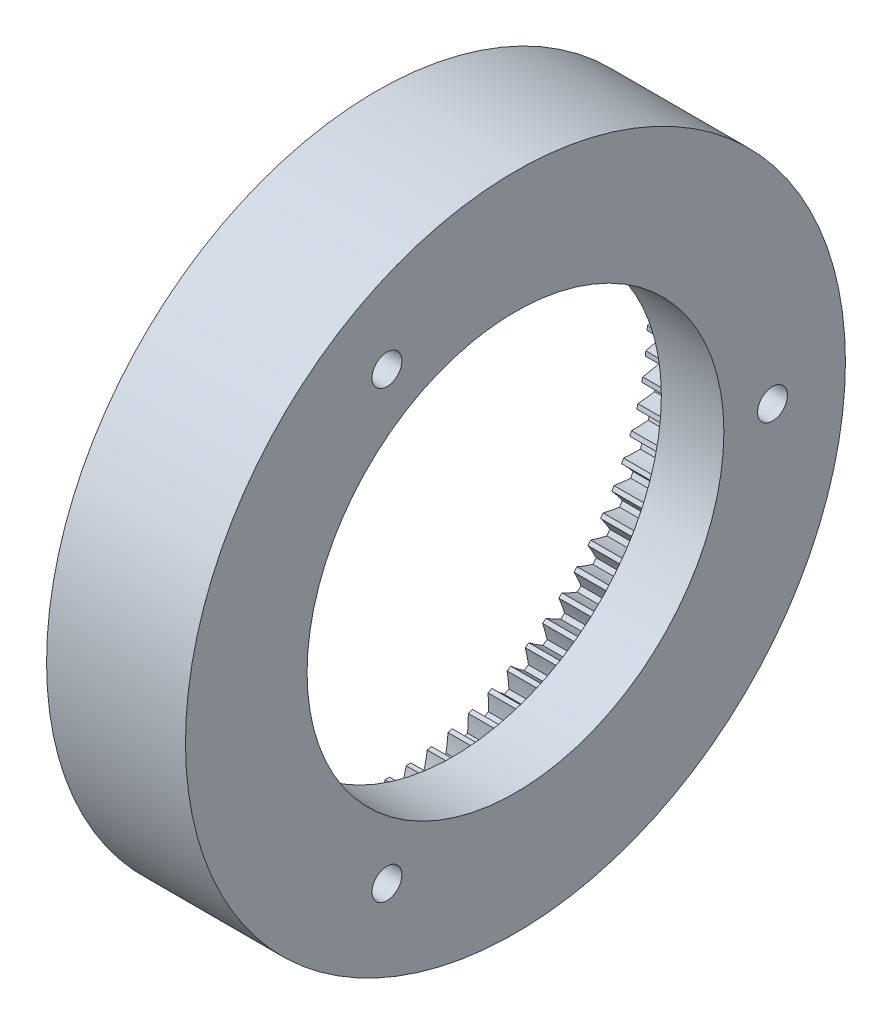
SolidWorks part; units mm, degrees
ref_plane "Plane1" through (0, 0, 0) normal (0, 0, 1) x (1, 0, 0)
ref_plane "Plane2" through (0, 0, 0) normal (0, 1, 0) x (1, 0, 0)
ref_plane "Plane3" through (0, 0, 0) normal (1, 0, 0) x (0, 0, -1)
other "Configuration Table"
sketch "HoldingSke" plane through (0, 0, 0) normal (0, 1, 0) x (1, 0, 0)
  line L0 (0, 0) -> (0.1736, -0.9848)
  line L1 (-15, 0) -> (100, 0) construction
  line L2 (0, 0) -> (-2.1039, 2.3779)
  line L3 (0, 0) -> (-11.863, 4.5341)
  line L4 (0, 0) -> (1.4996, 8.5048)
  line L5 (0, 0) -> (-23.7986, -8.8762)
  line L6 (0, 0) -> (-10.5278, -7.1032)
  line L7 (-2.1039, 2.3779) -> (3.3635, 27.1825)
  line L8 (-76.2, 3.3779) -> (-54.61, 3.3779)
  line L9 (-71.009, 38.7566) -> (-53.1078, 45.2721)
  line L10 (-76.2, 71.12) -> (104.1128, 71.12)
  line L11 (0, 0) -> (-10, 0)
  line L12 (-76.2, 101.6) -> (-76.162, 101.6)
  line L13 (24.9733, 27.94) -> (52.9518, 28.4284)
  line L14 (24.9733, 27.94) -> (24.9743, 27.94)
  line L15 (24.9733, 27.94) -> (100.4006, 29.5858)
  circle A0 centre (0, 0) radius 47.5
  circle A1 centre (0, 0) radius 12.7
  circle A2 centre (0, 0) radius 12.7
  dimension "Num_teeth" = 80
  dimension "Pitch_radius" = 180.3128
  dimension "Width" = 10
  dimension "Diameter" = 95
sketch "BasProSke" plane through (0, 0, 0) normal (0, 1, 0) x (1, 0, 0)
  line L0 (-10, 0) -> (60, 0) construction
  line L1 (0, 39) -> (0, 47.5)
  line L2 (0, 39) -> (10, 39)
  line L3 (10, 39) -> (10, 47.5)
  line L4 (10, 47.5) -> (0, 47.5)
  dimension "Thickness" = 10
  dimension "Diameter" = 95
revolve "Base-Revolve" add sketch "BasProSke" angle 360 about L0
sketch "TooCutSke" plane through (0, 0, 0) normal (1, 0, 0) x (0, 0, -1)
  line L3 (0.8803, 39.9903) -> (0.8803, 53.6633) construction
  line L4 (0, 0) -> (0, 59.563) construction
  line L5 (0, 0) -> (-2.6825, 68.2748) construction
  line L6 (-17.914, 33.1512) -> (36.4855, 35.2886) construction
  circle A0 centre (0, 0) radius 40 construction
  circle A1 centre (0, 0) radius 41.251 construction
  circle A2 centre (0, 0) radius 33.8289 construction
  circle A3 centre (0, 0) radius 38.9746 construction
  arc A4 (1.2253, 38.9553) -> (0.3732, 41.2493) centre (-17.914, 33.1512) ccw
  arc A5 (1.2253, 38.9553) -> (-1.2253, 38.9553) centre (0, 0) ccw
  arc A6 (0.3732, 41.2493) -> (-0.3732, 41.2493) centre (0, 0) ccw
  arc A7 (-0.3732, 41.2493) -> (-1.2253, 38.9553) centre (17.914, 33.1512) ccw
extrude "ToothCut" cut sketch "TooCutSke" along normal through all
fillet "Breaks" [suppressed] radius 0.1
fillet "RootFillets" [suppressed] radius 0.251
pattern_circular "TeethCuts" count 80 every 4.5 about axis through (-10, 0, 0) along (1, 0, 0) of "RootFillets", "Breaks", "ToothCut"
sketch "Sketch1" plane through (10, 0, 0) normal (1, 0, 0) x (0, 0, -1)
  circle A1 centre (0, 0) radius 47.5
  circle A2 centre (0, 0) radius 47.5
  arc A322 (2.8643, 41.1514) -> (1.8447, 38.9564) centre (20.4598, 31.6435) ccw
  arc A323 (3.6084, 41.0929) -> (2.8643, 41.1514) centre (0, 0) ccw
  arc A324 (4.2722, 38.7653) -> (3.6084, 41.0929) centre (-15.2577, 34.4545) ccw
  arc A325 (4.8955, 38.6915) -> (4.2722, 38.7653) centre (0, 0) ccw
  arc A326 (6.0842, 40.7998) -> (4.8955, 38.6915) centre (22.8794, 29.9407) ccw
  arc A327 (6.8214, 40.6831) -> (6.0842, 40.7998) centre (0, 0) ccw
  arc A328 (7.3005, 38.3106) -> (6.8214, 40.6831) centre (-12.5074, 35.5454) ccw
  arc A329 (7.9161, 38.1882) -> (7.3005, 38.3106) centre (0, 0) ccw
  arc A330 (9.2666, 40.1967) -> (7.9161, 38.1882) centre (25.158, 28.0533) ccw
  arc A331 (9.9923, 40.0225) -> (9.2666, 40.1967) centre (0, 0) ccw
  arc A332 (10.2838, 37.6197) -> (9.9923, 40.0225) centre (-9.68, 36.4172) ccw
  arc A333 (10.8879, 37.4494) -> (10.2838, 37.6197) centre (0, 0) ccw
  arc A334 (12.3918, 39.3458) -> (10.8879, 37.4494) centre (27.2815, 25.9929) ccw
  arc A335 (13.1017, 39.1151) -> (12.3918, 39.3458) centre (0, 0) ccw
  arc A336 (13.2037, 36.6969) -> (13.1017, 39.1151) centre (-6.7929, 37.0644) ccw
  arc A337 (13.7926, 36.4797) -> (13.2037, 36.6969) centre (0, 0) ccw
  arc A338 (15.4406, 38.2522) -> (13.7926, 36.4797) centre (29.2368, 23.7723) ccw
  arc A339 (16.1302, 37.9666) -> (15.4406, 38.2522) centre (0, 0) ccw
  arc A340 (16.0422, 35.5478) -> (16.1302, 37.9666) centre (-3.8639, 37.4831) ccw
  arc A341 (16.6122, 35.2851) -> (16.0422, 35.5478) centre (0, 0) ccw
  arc A342 (18.3943, 36.9228) -> (16.6122, 35.2851) centre (31.0118, 21.4052) ccw
  arc A343 (19.0593, 36.584) -> (18.3943, 36.9228) centre (0, 0) ccw
  arc A344 (18.7818, 34.1796) -> (19.0593, 36.584) centre (-0.9111, 37.6707) ccw
  arc A345 (19.3294, 33.8729) -> (18.7818, 34.1796) centre (0, 0) ccw
  arc A346 (21.2345, 35.3658) -> (19.3294, 33.8729) centre (32.5956, 18.906) ccw
  arc A347 (21.8709, 34.9758) -> (21.2345, 35.3658) centre (0, 0) ccw
  arc A348 (21.4056, 32.6006) -> (21.8709, 34.9758) centre (2.0473, 37.6261) ccw
  arc A349 (21.9275, 32.2519) -> (21.4056, 32.6006) centre (0, 0) ccw
  arc A350 (23.9438, 33.5908) -> (21.9275, 32.2519) centre (33.9785, 16.2903) ccw
  arc A351 (24.5477, 33.152) -> (23.9438, 33.5908) centre (0, 0) ccw
  arc A352 (23.8974, 30.8207) -> (24.5477, 33.152) centre (4.9931, 37.3494) ccw
  arc A353 (24.3903, 30.4321) -> (23.8974, 30.8207) centre (0, 0) ccw
  arc A354 (26.5055, 31.6086) -> (24.3903, 30.4321) centre (35.1519, 13.5742) ccw
  arc A355 (27.0731, 31.1239) -> (26.5055, 31.6086) centre (0, 0) ccw
  arc A356 (26.2419, 28.8507) -> (27.0731, 31.1239) centre (7.9081, 36.8426) ccw
  arc A357 (26.7028, 28.4246) -> (26.2419, 28.8507) centre (0, 0) ccw
  arc A358 (28.9038, 29.4316) -> (26.7028, 28.4246) centre (36.1085, 10.7743) ccw
  arc A359 (29.4316, 28.9038) -> (28.9038, 29.4316) centre (0, 0) ccw
  arc A360 (28.4246, 26.7028) -> (29.4316, 28.9038) centre (10.7743, 36.1085) ccw
  arc A361 (28.8507, 26.2419) -> (28.4246, 26.7028) centre (0, 0) ccw
  arc A362 (31.1239, 27.0731) -> (28.8507, 26.2419) centre (36.8426, 7.9081) ccw
  arc A363 (31.6086, 26.5055) -> (31.1239, 27.0731) centre (0, 0) ccw
  arc A364 (30.4321, 24.3903) -> (31.6086, 26.5055) centre (13.5742, 35.1519) ccw
  arc A365 (30.8207, 23.8974) -> (30.4321, 24.3903) centre (0, 0) ccw
  arc A366 (33.152, 24.5477) -> (30.8207, 23.8974) centre (37.3494, 4.9931) ccw
  arc A367 (33.5908, 23.9438) -> (33.152, 24.5477) centre (0, 0) ccw
  arc A368 (32.2519, 21.9275) -> (33.5908, 23.9438) centre (16.2903, 33.9785) ccw
  arc A369 (32.6006, 21.4056) -> (32.2519, 21.9275) centre (0, 0) ccw
  arc A370 (34.9758, 21.8709) -> (32.6006, 21.4056) centre (37.6261, 2.0473) ccw
  arc A371 (35.3658, 21.2345) -> (34.9758, 21.8709) centre (0, 0) ccw
  arc A372 (33.8729, 19.3294) -> (35.3658, 21.2345) centre (18.906, 32.5956) ccw
  arc A373 (34.1796, 18.7818) -> (33.8729, 19.3294) centre (0, 0) ccw
  arc A374 (36.584, 19.0593) -> (34.1796, 18.7818) centre (37.6707, -0.9111) ccw
  arc A375 (36.9228, 18.3943) -> (36.584, 19.0593) centre (0, 0) ccw
  arc A376 (35.2851, 16.6122) -> (36.9228, 18.3943) centre (21.4052, 31.0118) ccw
  arc A377 (35.5478, 16.0422) -> (35.2851, 16.6122) centre (0, 0) ccw
  arc A378 (37.9666, 16.1302) -> (35.5478, 16.0422) centre (37.4831, -3.8639) ccw
  arc A379 (38.2522, 15.4406) -> (37.9666, 16.1302) centre (0, 0) ccw
  arc A380 (36.4797, 13.7926) -> (38.2522, 15.4406) centre (23.7723, 29.2368) ccw
  arc A381 (36.6969, 13.2037) -> (36.4797, 13.7926) centre (0, 0) ccw
  arc A382 (39.1151, 13.1017) -> (36.6969, 13.2037) centre (37.0644, -6.7929) ccw
  arc A383 (39.3458, 12.3918) -> (39.1151, 13.1017) centre (0, 0) ccw
  arc A384 (37.4494, 10.8879) -> (39.3458, 12.3918) centre (25.9929, 27.2815) ccw
  arc A385 (37.6197, 10.2838) -> (37.4494, 10.8879) centre (0, 0) ccw
  arc A386 (40.0225, 9.9923) -> (37.6197, 10.2838) centre (36.4172, -9.68) ccw
  arc A387 (40.1967, 9.2666) -> (40.0225, 9.9923) centre (0, 0) ccw
  arc A388 (38.1882, 7.9161) -> (40.1967, 9.2666) centre (28.0533, 25.158) ccw
  arc A389 (38.3106, 7.3005) -> (38.1882, 7.9161) centre (0, 0) ccw
  arc A390 (40.6831, 6.8214) -> (38.3106, 7.3005) centre (35.5454, -12.5074) ccw
  arc A391 (40.7998, 6.0842) -> (40.6831, 6.8214) centre (0, 0) ccw
  arc A392 (38.6915, 4.8955) -> (40.7998, 6.0842) centre (29.9407, 22.8794) ccw
  arc A393 (38.7653, 4.2722) -> (38.6915, 4.8955) centre (0, 0) ccw
  arc A394 (41.0929, 3.6084) -> (38.7653, 4.2722) centre (34.4545, -15.2577) ccw
  arc A395 (41.1514, 2.8643) -> (41.0929, 3.6084) centre (0, 0) ccw
  arc A396 (38.9564, 1.8447) -> (41.1514, 2.8643) centre (31.6435, 20.4598) ccw
  arc A397 (38.981, 1.2175) -> (38.9564, 1.8447) centre (0, 0) ccw
  arc A398 (41.2493, 0.3732) -> (38.981, 1.2175) centre (33.1512, -17.914) ccw
  arc A399 (41.2493, -0.3732) -> (41.2493, 0.3732) centre (0, 0) ccw
  arc A400 (38.981, -1.2175) -> (41.2493, -0.3732) centre (33.1512, 17.914) ccw
  arc A401 (38.9564, -1.8447) -> (38.981, -1.2175) centre (0, 0) ccw
  arc A402 (41.1514, -2.8643) -> (38.9564, -1.8447) centre (31.6435, -20.4598) ccw
  arc A403 (41.0929, -3.6084) -> (41.1514, -2.8643) centre (0, 0) ccw
  arc A404 (38.7653, -4.2722) -> (41.0929, -3.6084) centre (34.4545, 15.2577) ccw
  arc A405 (38.6915, -4.8955) -> (38.7653, -4.2722) centre (0, 0) ccw
  arc A406 (40.7998, -6.0842) -> (38.6915, -4.8955) centre (29.9407, -22.8794) ccw
  arc A407 (40.6831, -6.8214) -> (40.7998, -6.0842) centre (0, 0) ccw
  arc A408 (38.3106, -7.3005) -> (40.6831, -6.8214) centre (35.5454, 12.5074) ccw
  arc A409 (38.1882, -7.9161) -> (38.3106, -7.3005) centre (0, 0) ccw
  arc A410 (40.1967, -9.2666) -> (38.1882, -7.9161) centre (28.0533, -25.158) ccw
  arc A411 (40.0225, -9.9923) -> (40.1967, -9.2666) centre (0, 0) ccw
  arc A412 (37.6197, -10.2838) -> (40.0225, -9.9923) centre (36.4172, 9.68) ccw
  arc A413 (37.4494, -10.8879) -> (37.6197, -10.2838) centre (0, 0) ccw
  arc A414 (39.3458, -12.3918) -> (37.4494, -10.8879) centre (25.9929, -27.2815) ccw
  arc A415 (39.1151, -13.1017) -> (39.3458, -12.3918) centre (0, 0) ccw
  arc A416 (36.6969, -13.2037) -> (39.1151, -13.1017) centre (37.0644, 6.7929) ccw
  arc A417 (36.4797, -13.7926) -> (36.6969, -13.2037) centre (0, 0) ccw
  arc A418 (38.2522, -15.4406) -> (36.4797, -13.7926) centre (23.7723, -29.2368) ccw
  arc A419 (37.9666, -16.1302) -> (38.2522, -15.4406) centre (0, 0) ccw
  arc A420 (35.5478, -16.0422) -> (37.9666, -16.1302) centre (37.4831, 3.8639) ccw
  arc A421 (35.2851, -16.6122) -> (35.5478, -16.0422) centre (0, 0) ccw
  arc A422 (36.9228, -18.3943) -> (35.2851, -16.6122) centre (21.4052, -31.0118) ccw
  arc A423 (36.584, -19.0593) -> (36.9228, -18.3943) centre (0, 0) ccw
  arc A424 (34.1796, -18.7818) -> (36.584, -19.0593) centre (37.6707, 0.9111) ccw
  arc A425 (33.8729, -19.3294) -> (34.1796, -18.7818) centre (0, 0) ccw
  arc A426 (35.3658, -21.2345) -> (33.8729, -19.3294) centre (18.906, -32.5956) ccw
  arc A427 (34.9758, -21.8709) -> (35.3658, -21.2345) centre (0, 0) ccw
  arc A428 (32.6006, -21.4056) -> (34.9758, -21.8709) centre (37.6261, -2.0473) ccw
  arc A429 (32.2519, -21.9275) -> (32.6006, -21.4056) centre (0, 0) ccw
  arc A430 (33.5908, -23.9438) -> (32.2519, -21.9275) centre (16.2903, -33.9785) ccw
  arc A431 (33.152, -24.5477) -> (33.5908, -23.9438) centre (0, 0) ccw
  arc A432 (30.8207, -23.8974) -> (33.152, -24.5477) centre (37.3494, -4.9931) ccw
  arc A433 (30.4321, -24.3903) -> (30.8207, -23.8974) centre (0, 0) ccw
  arc A434 (31.6086, -26.5055) -> (30.4321, -24.3903) centre (13.5742, -35.1519) ccw
  arc A435 (31.1239, -27.0731) -> (31.6086, -26.5055) centre (0, 0) ccw
  arc A436 (28.8507, -26.2419) -> (31.1239, -27.0731) centre (36.8426, -7.9081) ccw
  arc A437 (28.4246, -26.7028) -> (28.8507, -26.2419) centre (0, 0) ccw
  arc A438 (29.4316, -28.9038) -> (28.4246, -26.7028) centre (10.7743, -36.1085) ccw
  arc A439 (28.9038, -29.4316) -> (29.4316, -28.9038) centre (0, 0) ccw
  arc A440 (26.7028, -28.4246) -> (28.9038, -29.4316) centre (36.1085, -10.7743) ccw
  arc A441 (26.2419, -28.8507) -> (26.7028, -28.4246) centre (0, 0) ccw
  arc A442 (27.0731, -31.1239) -> (26.2419, -28.8507) centre (7.9081, -36.8426) ccw
  arc A443 (26.5055, -31.6086) -> (27.0731, -31.1239) centre (0, 0) ccw
  arc A444 (24.3903, -30.4321) -> (26.5055, -31.6086) centre (35.1519, -13.5742) ccw
  arc A445 (23.8974, -30.8207) -> (24.3903, -30.4321) centre (0, 0) ccw
  arc A446 (24.5477, -33.152) -> (23.8974, -30.8207) centre (4.9931, -37.3494) ccw
  arc A447 (23.9438, -33.5908) -> (24.5477, -33.152) centre (0, 0) ccw
  arc A448 (21.9275, -32.2519) -> (23.9438, -33.5908) centre (33.9785, -16.2903) ccw
  arc A449 (21.4056, -32.6006) -> (21.9275, -32.2519) centre (0, 0) ccw
  arc A450 (21.8709, -34.9758) -> (21.4056, -32.6006) centre (2.0473, -37.6261) ccw
  arc A451 (21.2345, -35.3658) -> (21.8709, -34.9758) centre (0, 0) ccw
  arc A452 (19.3294, -33.8729) -> (21.2345, -35.3658) centre (32.5956, -18.906) ccw
  arc A453 (18.7818, -34.1796) -> (19.3294, -33.8729) centre (0, 0) ccw
  arc A454 (19.0593, -36.584) -> (18.7818, -34.1796) centre (-0.9111, -37.6707) ccw
  arc A455 (18.3943, -36.9228) -> (19.0593, -36.584) centre (0, 0) ccw
  arc A456 (16.6122, -35.2851) -> (18.3943, -36.9228) centre (31.0118, -21.4052) ccw
  arc A457 (16.0422, -35.5478) -> (16.6122, -35.2851) centre (0, 0) ccw
  arc A458 (16.1302, -37.9666) -> (16.0422, -35.5478) centre (-3.8639, -37.4831) ccw
  arc A459 (15.4406, -38.2522) -> (16.1302, -37.9666) centre (0, 0) ccw
  arc A460 (13.7926, -36.4797) -> (15.4406, -38.2522) centre (29.2368, -23.7723) ccw
  arc A461 (13.2037, -36.6969) -> (13.7926, -36.4797) centre (0, 0) ccw
  arc A462 (13.1017, -39.1151) -> (13.2037, -36.6969) centre (-6.7929, -37.0644) ccw
  arc A463 (12.3918, -39.3458) -> (13.1017, -39.1151) centre (0, 0) ccw
  arc A464 (10.8879, -37.4494) -> (12.3918, -39.3458) centre (27.2815, -25.9929) ccw
  arc A465 (10.2838, -37.6197) -> (10.8879, -37.4494) centre (0, 0) ccw
  arc A466 (9.9923, -40.0225) -> (10.2838, -37.6197) centre (-9.68, -36.4172) ccw
  arc A467 (9.2666, -40.1967) -> (9.9923, -40.0225) centre (0, 0) ccw
  arc A468 (7.9161, -38.1882) -> (9.2666, -40.1967) centre (25.158, -28.0533) ccw
  arc A469 (7.3005, -38.3106) -> (7.9161, -38.1882) centre (0, 0) ccw
  arc A470 (6.8214, -40.6831) -> (7.3005, -38.3106) centre (-12.5074, -35.5454) ccw
  arc A471 (6.0842, -40.7998) -> (6.8214, -40.6831) centre (0, 0) ccw
  arc A472 (4.8955, -38.6915) -> (6.0842, -40.7998) centre (22.8794, -29.9407) ccw
  arc A473 (4.2722, -38.7653) -> (4.8955, -38.6915) centre (0, 0) ccw
  arc A474 (3.6084, -41.0929) -> (4.2722, -38.7653) centre (-15.2577, -34.4545) ccw
  arc A475 (2.8643, -41.1514) -> (3.6084, -41.0929) centre (0, 0) ccw
  arc A476 (1.8447, -38.9564) -> (2.8643, -41.1514) centre (20.4598, -31.6435) ccw
  arc A477 (1.2175, -38.981) -> (1.8447, -38.9564) centre (0, 0) ccw
  arc A478 (0.3732, -41.2493) -> (1.2175, -38.981) centre (-17.914, -33.1512) ccw
  arc A479 (-0.3732, -41.2493) -> (0.3732, -41.2493) centre (0, 0) ccw
  arc A480 (-1.2175, -38.981) -> (-0.3732, -41.2493) centre (17.914, -33.1512) ccw
  arc A481 (-1.8447, -38.9564) -> (-1.2175, -38.981) centre (0, 0) ccw
  arc A482 (-2.8643, -41.1514) -> (-1.8447, -38.9564) centre (-20.4598, -31.6435) ccw
  arc A483 (-3.6084, -41.0929) -> (-2.8643, -41.1514) centre (0, 0) ccw
  arc A484 (-4.2722, -38.7653) -> (-3.6084, -41.0929) centre (15.2577, -34.4545) ccw
  arc A485 (-4.8955, -38.6915) -> (-4.2722, -38.7653) centre (0, 0) ccw
  arc A486 (-6.0842, -40.7998) -> (-4.8955, -38.6915) centre (-22.8794, -29.9407) ccw
  arc A487 (-6.8214, -40.6831) -> (-6.0842, -40.7998) centre (0, 0) ccw
  arc A488 (-7.3005, -38.3106) -> (-6.8214, -40.6831) centre (12.5074, -35.5454) ccw
  arc A489 (-7.9161, -38.1882) -> (-7.3005, -38.3106) centre (0, 0) ccw
  arc A490 (-9.2666, -40.1967) -> (-7.9161, -38.1882) centre (-25.158, -28.0533) ccw
  arc A491 (-9.9923, -40.0225) -> (-9.2666, -40.1967) centre (0, 0) ccw
  arc A492 (-10.2838, -37.6197) -> (-9.9923, -40.0225) centre (9.68, -36.4172) ccw
  arc A493 (-10.8879, -37.4494) -> (-10.2838, -37.6197) centre (0, 0) ccw
  arc A494 (-12.3918, -39.3458) -> (-10.8879, -37.4494) centre (-27.2815, -25.9929) ccw
  arc A495 (-13.1017, -39.1151) -> (-12.3918, -39.3458) centre (0, 0) ccw
  arc A496 (-13.2037, -36.6969) -> (-13.1017, -39.1151) centre (6.7929, -37.0644) ccw
  arc A497 (-13.7926, -36.4797) -> (-13.2037, -36.6969) centre (0, 0) ccw
  arc A498 (-15.4406, -38.2522) -> (-13.7926, -36.4797) centre (-29.2368, -23.7723) ccw
  arc A499 (-16.1302, -37.9666) -> (-15.4406, -38.2522) centre (0, 0) ccw
  arc A500 (-16.0422, -35.5478) -> (-16.1302, -37.9666) centre (3.8639, -37.4831) ccw
  arc A501 (-16.6122, -35.2851) -> (-16.0422, -35.5478) centre (0, 0) ccw
  arc A502 (-18.3943, -36.9228) -> (-16.6122, -35.2851) centre (-31.0118, -21.4052) ccw
  arc A503 (-19.0593, -36.584) -> (-18.3943, -36.9228) centre (0, 0) ccw
  arc A504 (-18.7818, -34.1796) -> (-19.0593, -36.584) centre (0.9111, -37.6707) ccw
  arc A505 (-19.3294, -33.8729) -> (-18.7818, -34.1796) centre (0, 0) ccw
  arc A506 (-21.2345, -35.3658) -> (-19.3294, -33.8729) centre (-32.5956, -18.906) ccw
  arc A507 (-21.8709, -34.9758) -> (-21.2345, -35.3658) centre (0, 0) ccw
  arc A508 (-21.4056, -32.6006) -> (-21.8709, -34.9758) centre (-2.0473, -37.6261) ccw
  arc A509 (-21.9275, -32.2519) -> (-21.4056, -32.6006) centre (0, 0) ccw
  arc A510 (-23.9438, -33.5908) -> (-21.9275, -32.2519) centre (-33.9785, -16.2903) ccw
  arc A511 (-24.5477, -33.152) -> (-23.9438, -33.5908) centre (0, 0) ccw
  arc A512 (-23.8974, -30.8207) -> (-24.5477, -33.152) centre (-4.9931, -37.3494) ccw
  arc A513 (-24.3903, -30.4321) -> (-23.8974, -30.8207) centre (0, 0) ccw
  arc A514 (-26.5055, -31.6086) -> (-24.3903, -30.4321) centre (-35.1519, -13.5742) ccw
  arc A515 (-27.0731, -31.1239) -> (-26.5055, -31.6086) centre (0, 0) ccw
  arc A516 (-26.2419, -28.8507) -> (-27.0731, -31.1239) centre (-7.9081, -36.8426) ccw
  arc A517 (-26.7028, -28.4246) -> (-26.2419, -28.8507) centre (0, 0) ccw
  arc A518 (-28.9038, -29.4316) -> (-26.7028, -28.4246) centre (-36.1085, -10.7743) ccw
  arc A519 (-29.4316, -28.9038) -> (-28.9038, -29.4316) centre (0, 0) ccw
  arc A520 (-28.4246, -26.7028) -> (-29.4316, -28.9038) centre (-10.7743, -36.1085) ccw
  arc A521 (-28.8507, -26.2419) -> (-28.4246, -26.7028) centre (0, 0) ccw
  arc A522 (-31.1239, -27.0731) -> (-28.8507, -26.2419) centre (-36.8426, -7.9081) ccw
  arc A523 (-31.6086, -26.5055) -> (-31.1239, -27.0731) centre (0, 0) ccw
  arc A524 (-30.4321, -24.3903) -> (-31.6086, -26.5055) centre (-13.5742, -35.1519) ccw
  arc A525 (-30.8207, -23.8974) -> (-30.4321, -24.3903) centre (0, 0) ccw
  arc A526 (-33.152, -24.5477) -> (-30.8207, -23.8974) centre (-37.3494, -4.9931) ccw
  arc A527 (-33.5908, -23.9438) -> (-33.152, -24.5477) centre (0, 0) ccw
  arc A528 (-32.2519, -21.9275) -> (-33.5908, -23.9438) centre (-16.2903, -33.9785) ccw
  arc A529 (-32.6006, -21.4056) -> (-32.2519, -21.9275) centre (0, 0) ccw
  arc A530 (-34.9758, -21.8709) -> (-32.6006, -21.4056) centre (-37.6261, -2.0473) ccw
  arc A531 (-35.3658, -21.2345) -> (-34.9758, -21.8709) centre (0, 0) ccw
  arc A532 (-33.8729, -19.3294) -> (-35.3658, -21.2345) centre (-18.906, -32.5956) ccw
  arc A533 (-34.1796, -18.7818) -> (-33.8729, -19.3294) centre (0, 0) ccw
  arc A534 (-36.584, -19.0593) -> (-34.1796, -18.7818) centre (-37.6707, 0.9111) ccw
  arc A535 (-36.9228, -18.3943) -> (-36.584, -19.0593) centre (0, 0) ccw
  arc A536 (-35.2851, -16.6122) -> (-36.9228, -18.3943) centre (-21.4052, -31.0118) ccw
  arc A537 (-35.5478, -16.0422) -> (-35.2851, -16.6122) centre (0, 0) ccw
  arc A538 (-37.9666, -16.1302) -> (-35.5478, -16.0422) centre (-37.4831, 3.8639) ccw
  arc A539 (-38.2522, -15.4406) -> (-37.9666, -16.1302) centre (0, 0) ccw
  arc A540 (-36.4797, -13.7926) -> (-38.2522, -15.4406) centre (-23.7723, -29.2368) ccw
  arc A541 (-36.6969, -13.2037) -> (-36.4797, -13.7926) centre (0, 0) ccw
  arc A542 (-39.1151, -13.1017) -> (-36.6969, -13.2037) centre (-37.0644, 6.7929) ccw
  arc A543 (-39.3458, -12.3918) -> (-39.1151, -13.1017) centre (0, 0) ccw
  arc A544 (-37.4494, -10.8879) -> (-39.3458, -12.3918) centre (-25.9929, -27.2815) ccw
  arc A545 (-37.6197, -10.2838) -> (-37.4494, -10.8879) centre (0, 0) ccw
  arc A546 (-40.0225, -9.9923) -> (-37.6197, -10.2838) centre (-36.4172, 9.68) ccw
  arc A547 (-40.1967, -9.2666) -> (-40.0225, -9.9923) centre (0, 0) ccw
  arc A548 (-38.1882, -7.9161) -> (-40.1967, -9.2666) centre (-28.0533, -25.158) ccw
  arc A549 (-38.3106, -7.3005) -> (-38.1882, -7.9161) centre (0, 0) ccw
  arc A550 (-40.6831, -6.8214) -> (-38.3106, -7.3005) centre (-35.5454, 12.5074) ccw
  arc A551 (-40.7998, -6.0842) -> (-40.6831, -6.8214) centre (0, 0) ccw
  arc A552 (-38.6915, -4.8955) -> (-40.7998, -6.0842) centre (-29.9407, -22.8794) ccw
  arc A553 (-38.7653, -4.2722) -> (-38.6915, -4.8955) centre (0, 0) ccw
  arc A554 (-41.0929, -3.6084) -> (-38.7653, -4.2722) centre (-34.4545, 15.2577) ccw
  arc A555 (-41.1514, -2.8643) -> (-41.0929, -3.6084) centre (0, 0) ccw
  arc A556 (-38.9564, -1.8447) -> (-41.1514, -2.8643) centre (-31.6435, -20.4598) ccw
  arc A557 (-38.981, -1.2175) -> (-38.9564, -1.8447) centre (0, 0) ccw
  arc A558 (-41.2493, -0.3732) -> (-38.981, -1.2175) centre (-33.1512, 17.914) ccw
  arc A559 (-41.2493, 0.3732) -> (-41.2493, -0.3732) centre (0, 0) ccw
  arc A560 (-38.981, 1.2175) -> (-41.2493, 0.3732) centre (-33.1512, -17.914) ccw
  arc A561 (-38.9564, 1.8447) -> (-38.981, 1.2175) centre (0, 0) ccw
  arc A562 (-41.1514, 2.8643) -> (-38.9564, 1.8447) centre (-31.6435, 20.4598) ccw
  arc A563 (-41.0929, 3.6084) -> (-41.1514, 2.8643) centre (0, 0) ccw
  arc A564 (-38.7653, 4.2722) -> (-41.0929, 3.6084) centre (-34.4545, -15.2577) ccw
  arc A565 (-38.6915, 4.8955) -> (-38.7653, 4.2722) centre (0, 0) ccw
  arc A566 (-40.7998, 6.0842) -> (-38.6915, 4.8955) centre (-29.9407, 22.8794) ccw
  arc A567 (-40.6831, 6.8214) -> (-40.7998, 6.0842) centre (0, 0) ccw
  arc A568 (-38.3106, 7.3005) -> (-40.6831, 6.8214) centre (-35.5454, -12.5074) ccw
  arc A569 (-38.1882, 7.9161) -> (-38.3106, 7.3005) centre (0, 0) ccw
  arc A570 (-40.1967, 9.2666) -> (-38.1882, 7.9161) centre (-28.0533, 25.158) ccw
  arc A571 (-40.0225, 9.9923) -> (-40.1967, 9.2666) centre (0, 0) ccw
  arc A572 (-37.6197, 10.2838) -> (-40.0225, 9.9923) centre (-36.4172, -9.68) ccw
  arc A573 (-37.4494, 10.8879) -> (-37.6197, 10.2838) centre (0, 0) ccw
  arc A574 (-39.3458, 12.3918) -> (-37.4494, 10.8879) centre (-25.9929, 27.2815) ccw
  arc A575 (-39.1151, 13.1017) -> (-39.3458, 12.3918) centre (0, 0) ccw
  arc A576 (-36.6969, 13.2037) -> (-39.1151, 13.1017) centre (-37.0644, -6.7929) ccw
  arc A577 (-36.4797, 13.7926) -> (-36.6969, 13.2037) centre (0, 0) ccw
  arc A578 (-38.2522, 15.4406) -> (-36.4797, 13.7926) centre (-23.7723, 29.2368) ccw
  arc A579 (-37.9666, 16.1302) -> (-38.2522, 15.4406) centre (0, 0) ccw
  arc A580 (-35.5478, 16.0422) -> (-37.9666, 16.1302) centre (-37.4831, -3.8639) ccw
  arc A581 (-35.2851, 16.6122) -> (-35.5478, 16.0422) centre (0, 0) ccw
  arc A582 (-36.9228, 18.3943) -> (-35.2851, 16.6122) centre (-21.4052, 31.0118) ccw
  arc A583 (-36.584, 19.0593) -> (-36.9228, 18.3943) centre (0, 0) ccw
  arc A584 (-34.1796, 18.7818) -> (-36.584, 19.0593) centre (-37.6707, -0.9111) ccw
  arc A585 (-33.8729, 19.3294) -> (-34.1796, 18.7818) centre (0, 0) ccw
  arc A586 (-35.3658, 21.2345) -> (-33.8729, 19.3294) centre (-18.906, 32.5956) ccw
  arc A587 (-34.9758, 21.8709) -> (-35.3658, 21.2345) centre (0, 0) ccw
  arc A588 (-32.6006, 21.4056) -> (-34.9758, 21.8709) centre (-37.6261, 2.0473) ccw
  arc A589 (-32.2519, 21.9275) -> (-32.6006, 21.4056) centre (0, 0) ccw
  arc A590 (-33.5908, 23.9438) -> (-32.2519, 21.9275) centre (-16.2903, 33.9785) ccw
  arc A591 (-33.152, 24.5477) -> (-33.5908, 23.9438) centre (0, 0) ccw
  arc A592 (-30.8207, 23.8974) -> (-33.152, 24.5477) centre (-37.3494, 4.9931) ccw
  arc A593 (-30.4321, 24.3903) -> (-30.8207, 23.8974) centre (0, 0) ccw
  arc A594 (-31.6086, 26.5055) -> (-30.4321, 24.3903) centre (-13.5742, 35.1519) ccw
  arc A595 (-31.1239, 27.0731) -> (-31.6086, 26.5055) centre (0, 0) ccw
  arc A596 (-28.8507, 26.2419) -> (-31.1239, 27.0731) centre (-36.8426, 7.9081) ccw
  arc A597 (-28.4246, 26.7028) -> (-28.8507, 26.2419) centre (0, 0) ccw
  arc A598 (-29.4316, 28.9038) -> (-28.4246, 26.7028) centre (-10.7743, 36.1085) ccw
  arc A599 (-28.9038, 29.4316) -> (-29.4316, 28.9038) centre (0, 0) ccw
  arc A600 (-26.7028, 28.4246) -> (-28.9038, 29.4316) centre (-36.1085, 10.7743) ccw
  arc A601 (-26.2419, 28.8507) -> (-26.7028, 28.4246) centre (0, 0) ccw
  arc A602 (-27.0731, 31.1239) -> (-26.2419, 28.8507) centre (-7.9081, 36.8426) ccw
  arc A603 (-26.5055, 31.6086) -> (-27.0731, 31.1239) centre (0, 0) ccw
  arc A604 (-24.3903, 30.4321) -> (-26.5055, 31.6086) centre (-35.1519, 13.5742) ccw
  arc A605 (-23.8974, 30.8207) -> (-24.3903, 30.4321) centre (0, 0) ccw
  arc A606 (-24.5477, 33.152) -> (-23.8974, 30.8207) centre (-4.9931, 37.3494) ccw
  arc A607 (-23.9438, 33.5908) -> (-24.5477, 33.152) centre (0, 0) ccw
  arc A608 (-21.9275, 32.2519) -> (-23.9438, 33.5908) centre (-33.9785, 16.2903) ccw
  arc A609 (-21.4056, 32.6006) -> (-21.9275, 32.2519) centre (0, 0) ccw
  arc A610 (-21.8709, 34.9758) -> (-21.4056, 32.6006) centre (-2.0473, 37.6261) ccw
  arc A611 (-21.2345, 35.3658) -> (-21.8709, 34.9758) centre (0, 0) ccw
  arc A612 (-19.3294, 33.8729) -> (-21.2345, 35.3658) centre (-32.5956, 18.906) ccw
  arc A613 (-18.7818, 34.1796) -> (-19.3294, 33.8729) centre (0, 0) ccw
  arc A614 (-19.0593, 36.584) -> (-18.7818, 34.1796) centre (0.9111, 37.6707) ccw
  arc A615 (-18.3943, 36.9228) -> (-19.0593, 36.584) centre (0, 0) ccw
  arc A616 (-16.6122, 35.2851) -> (-18.3943, 36.9228) centre (-31.0118, 21.4052) ccw
  arc A617 (-16.0422, 35.5478) -> (-16.6122, 35.2851) centre (0, 0) ccw
  arc A618 (-16.1302, 37.9666) -> (-16.0422, 35.5478) centre (3.8639, 37.4831) ccw
  arc A619 (-15.4406, 38.2522) -> (-16.1302, 37.9666) centre (0, 0) ccw
  arc A620 (-13.7926, 36.4797) -> (-15.4406, 38.2522) centre (-29.2368, 23.7723) ccw
  arc A621 (-13.2037, 36.6969) -> (-13.7926, 36.4797) centre (0, 0) ccw
  arc A622 (-13.1017, 39.1151) -> (-13.2037, 36.6969) centre (6.7929, 37.0644) ccw
  arc A623 (-12.3918, 39.3458) -> (-13.1017, 39.1151) centre (0, 0) ccw
  arc A624 (-10.8879, 37.4494) -> (-12.3918, 39.3458) centre (-27.2815, 25.9929) ccw
  arc A625 (-10.2838, 37.6197) -> (-10.8879, 37.4494) centre (0, 0) ccw
  arc A626 (-9.9923, 40.0225) -> (-10.2838, 37.6197) centre (9.68, 36.4172) ccw
  arc A627 (-9.2666, 40.1967) -> (-9.9923, 40.0225) centre (0, 0) ccw
  arc A628 (-7.9161, 38.1882) -> (-9.2666, 40.1967) centre (-25.158, 28.0533) ccw
  arc A629 (-7.3005, 38.3106) -> (-7.9161, 38.1882) centre (0, 0) ccw
  arc A630 (-6.8214, 40.6831) -> (-7.3005, 38.3106) centre (12.5074, 35.5454) ccw
  arc A631 (-6.0842, 40.7998) -> (-6.8214, 40.6831) centre (0, 0) ccw
  arc A632 (-4.8955, 38.6915) -> (-6.0842, 40.7998) centre (-22.8794, 29.9407) ccw
  arc A633 (-4.2722, 38.7653) -> (-4.8955, 38.6915) centre (0, 0) ccw
  arc A634 (-3.6084, 41.0929) -> (-4.2722, 38.7653) centre (15.2577, 34.4545) ccw
  arc A635 (-2.8643, 41.1514) -> (-3.6084, 41.0929) centre (0, 0) ccw
  arc A636 (-1.8447, 38.9564) -> (-2.8643, 41.1514) centre (-20.4598, 31.6435) ccw
  arc A637 (-1.2175, 38.981) -> (-1.8447, 38.9564) centre (0, 0) ccw
  arc A638 (-0.3732, 41.2493) -> (-1.2175, 38.981) centre (17.914, 33.1512) ccw
  arc A639 (0.3732, 41.2493) -> (-0.3732, 41.2493) centre (0, 0) ccw
  arc A640 (1.2175, 38.981) -> (0.3732, 41.2493) centre (-17.914, 33.1512) ccw
  arc A641 (1.8447, 38.9564) -> (1.2175, 38.981) centre (0, 0) ccw
  arc A642 (2.8643, 41.1514) -> (1.8447, 38.9564) centre (20.4598, 31.6435) ccw
  arc A643 (3.6084, 41.0929) -> (2.8643, 41.1514) centre (0, 0) ccw
  arc A644 (4.2722, 38.7653) -> (3.6084, 41.0929) centre (-15.2577, 34.4545) ccw
  arc A645 (4.8955, 38.6915) -> (4.2722, 38.7653) centre (0, 0) ccw
  arc A646 (6.0842, 40.7998) -> (4.8955, 38.6915) centre (22.8794, 29.9407) ccw
  arc A647 (6.8214, 40.6831) -> (6.0842, 40.7998) centre (0, 0) ccw
  arc A648 (7.3005, 38.3106) -> (6.8214, 40.6831) centre (-12.5074, 35.5454) ccw
  arc A649 (7.9161, 38.1882) -> (7.3005, 38.3106) centre (0, 0) ccw
  arc A650 (9.2666, 40.1967) -> (7.9161, 38.1882) centre (25.158, 28.0533) ccw
  arc A651 (9.9923, 40.0225) -> (9.2666, 40.1967) centre (0, 0) ccw
  arc A652 (10.2838, 37.6197) -> (9.9923, 40.0225) centre (-9.68, 36.4172) ccw
  arc A653 (10.8879, 37.4494) -> (10.2838, 37.6197) centre (0, 0) ccw
  arc A654 (12.3918, 39.3458) -> (10.8879, 37.4494) centre (27.2815, 25.9929) ccw
  arc A655 (13.1017, 39.1151) -> (12.3918, 39.3458) centre (0, 0) ccw
  arc A656 (13.2037, 36.6969) -> (13.1017, 39.1151) centre (-6.7929, 37.0644) ccw
  arc A657 (13.7926, 36.4797) -> (13.2037, 36.6969) centre (0, 0) ccw
  arc A658 (15.4406, 38.2522) -> (13.7926, 36.4797) centre (29.2368, 23.7723) ccw
  arc A659 (16.1302, 37.9666) -> (15.4406, 38.2522) centre (0, 0) ccw
  arc A660 (16.0422, 35.5478) -> (16.1302, 37.9666) centre (-3.8639, 37.4831) ccw
  arc A661 (16.6122, 35.2851) -> (16.0422, 35.5478) centre (0, 0) ccw
  arc A662 (18.3943, 36.9228) -> (16.6122, 35.2851) centre (31.0118, 21.4052) ccw
  arc A663 (19.0593, 36.584) -> (18.3943, 36.9228) centre (0, 0) ccw
  arc A664 (18.7818, 34.1796) -> (19.0593, 36.584) centre (-0.9111, 37.6707) ccw
  arc A665 (19.3294, 33.8729) -> (18.7818, 34.1796) centre (0, 0) ccw
  arc A666 (21.2345, 35.3658) -> (19.3294, 33.8729) centre (32.5956, 18.906) ccw
  arc A667 (21.8709, 34.9758) -> (21.2345, 35.3658) centre (0, 0) ccw
  arc A668 (21.4056, 32.6006) -> (21.8709, 34.9758) centre (2.0473, 37.6261) ccw
  arc A669 (21.9275, 32.2519) -> (21.4056, 32.6006) centre (0, 0) ccw
  arc A670 (23.9438, 33.5908) -> (21.9275, 32.2519) centre (33.9785, 16.2903) ccw
  arc A671 (24.5477, 33.152) -> (23.9438, 33.5908) centre (0, 0) ccw
  arc A672 (23.8974, 30.8207) -> (24.5477, 33.152) centre (4.9931, 37.3494) ccw
  arc A673 (24.3903, 30.4321) -> (23.8974, 30.8207) centre (0, 0) ccw
  arc A674 (26.5055, 31.6086) -> (24.3903, 30.4321) centre (35.1519, 13.5742) ccw
  arc A675 (27.0731, 31.1239) -> (26.5055, 31.6086) centre (0, 0) ccw
  arc A676 (26.2419, 28.8507) -> (27.0731, 31.1239) centre (7.9081, 36.8426) ccw
  arc A677 (26.7028, 28.4246) -> (26.2419, 28.8507) centre (0, 0) ccw
  arc A678 (28.9038, 29.4316) -> (26.7028, 28.4246) centre (36.1085, 10.7743) ccw
  arc A679 (29.4316, 28.9038) -> (28.9038, 29.4316) centre (0, 0) ccw
  arc A680 (28.4246, 26.7028) -> (29.4316, 28.9038) centre (10.7743, 36.1085) ccw
  arc A681 (28.8507, 26.2419) -> (28.4246, 26.7028) centre (0, 0) ccw
  arc A682 (31.1239, 27.0731) -> (28.8507, 26.2419) centre (36.8426, 7.9081) ccw
  arc A683 (31.6086, 26.5055) -> (31.1239, 27.0731) centre (0, 0) ccw
  arc A684 (30.4321, 24.3903) -> (31.6086, 26.5055) centre (13.5742, 35.1519) ccw
  arc A685 (30.8207, 23.8974) -> (30.4321, 24.3903) centre (0, 0) ccw
  arc A686 (33.152, 24.5477) -> (30.8207, 23.8974) centre (37.3494, 4.9931) ccw
  arc A687 (33.5908, 23.9438) -> (33.152, 24.5477) centre (0, 0) ccw
  arc A688 (32.2519, 21.9275) -> (33.5908, 23.9438) centre (16.2903, 33.9785) ccw
  arc A689 (32.6006, 21.4056) -> (32.2519, 21.9275) centre (0, 0) ccw
  arc A690 (34.9758, 21.8709) -> (32.6006, 21.4056) centre (37.6261, 2.0473) ccw
  arc A691 (35.3658, 21.2345) -> (34.9758, 21.8709) centre (0, 0) ccw
  arc A692 (33.8729, 19.3294) -> (35.3658, 21.2345) centre (18.906, 32.5956) ccw
  arc A693 (34.1796, 18.7818) -> (33.8729, 19.3294) centre (0, 0) ccw
  arc A694 (36.584, 19.0593) -> (34.1796, 18.7818) centre (37.6707, -0.9111) ccw
  arc A695 (36.9228, 18.3943) -> (36.584, 19.0593) centre (0, 0) ccw
  arc A696 (35.2851, 16.6122) -> (36.9228, 18.3943) centre (21.4052, 31.0118) ccw
  arc A697 (35.5478, 16.0422) -> (35.2851, 16.6122) centre (0, 0) ccw
  arc A698 (37.9666, 16.1302) -> (35.5478, 16.0422) centre (37.4831, -3.8639) ccw
  arc A699 (38.2522, 15.4406) -> (37.9666, 16.1302) centre (0, 0) ccw
  arc A700 (36.4797, 13.7926) -> (38.2522, 15.4406) centre (23.7723, 29.2368) ccw
  arc A701 (36.6969, 13.2037) -> (36.4797, 13.7926) centre (0, 0) ccw
  arc A702 (39.1151, 13.1017) -> (36.6969, 13.2037) centre (37.0644, -6.7929) ccw
  arc A703 (39.3458, 12.3918) -> (39.1151, 13.1017) centre (0, 0) ccw
  arc A704 (37.4494, 10.8879) -> (39.3458, 12.3918) centre (25.9929, 27.2815) ccw
  arc A705 (37.6197, 10.2838) -> (37.4494, 10.8879) centre (0, 0) ccw
  arc A706 (40.0225, 9.9923) -> (37.6197, 10.2838) centre (36.4172, -9.68) ccw
  arc A707 (40.1967, 9.2666) -> (40.0225, 9.9923) centre (0, 0) ccw
  arc A708 (38.1882, 7.9161) -> (40.1967, 9.2666) centre (28.0533, 25.158) ccw
  arc A709 (38.3106, 7.3005) -> (38.1882, 7.9161) centre (0, 0) ccw
  arc A710 (40.6831, 6.8214) -> (38.3106, 7.3005) centre (35.5454, -12.5074) ccw
  arc A711 (40.7998, 6.0842) -> (40.6831, 6.8214) centre (0, 0) ccw
  arc A712 (38.6915, 4.8955) -> (40.7998, 6.0842) centre (29.9407, 22.8794) ccw
  arc A713 (38.7653, 4.2722) -> (38.6915, 4.8955) centre (0, 0) ccw
  arc A714 (41.0929, 3.6084) -> (38.7653, 4.2722) centre (34.4545, -15.2577) ccw
  arc A715 (41.1514, 2.8643) -> (41.0929, 3.6084) centre (0, 0) ccw
  arc A716 (38.9564, 1.8447) -> (41.1514, 2.8643) centre (31.6435, 20.4598) ccw
  arc A717 (38.981, 1.2175) -> (38.9564, 1.8447) centre (0, 0) ccw
  arc A718 (41.2493, 0.3732) -> (38.981, 1.2175) centre (33.1512, -17.914) ccw
  arc A719 (41.2493, -0.3732) -> (41.2493, 0.3732) centre (0, 0) ccw
  arc A720 (38.981, -1.2175) -> (41.2493, -0.3732) centre (33.1512, 17.914) ccw
  arc A721 (38.9564, -1.8447) -> (38.981, -1.2175) centre (0, 0) ccw
  arc A722 (41.1514, -2.8643) -> (38.9564, -1.8447) centre (31.6435, -20.4598) ccw
  arc A723 (41.0929, -3.6084) -> (41.1514, -2.8643) centre (0, 0) ccw
  arc A724 (38.7653, -4.2722) -> (41.0929, -3.6084) centre (34.4545, 15.2577) ccw
  arc A725 (38.6915, -4.8955) -> (38.7653, -4.2722) centre (0, 0) ccw
  arc A726 (40.7998, -6.0842) -> (38.6915, -4.8955) centre (29.9407, -22.8794) ccw
  arc A727 (40.6831, -6.8214) -> (40.7998, -6.0842) centre (0, 0) ccw
  arc A728 (38.3106, -7.3005) -> (40.6831, -6.8214) centre (35.5454, 12.5074) ccw
  arc A729 (38.1882, -7.9161) -> (38.3106, -7.3005) centre (0, 0) ccw
  arc A730 (40.1967, -9.2666) -> (38.1882, -7.9161) centre (28.0533, -25.158) ccw
  arc A731 (40.0225, -9.9923) -> (40.1967, -9.2666) centre (0, 0) ccw
  arc A732 (37.6197, -10.2838) -> (40.0225, -9.9923) centre (36.4172, 9.68) ccw
  arc A733 (37.4494, -10.8879) -> (37.6197, -10.2838) centre (0, 0) ccw
  arc A734 (39.3458, -12.3918) -> (37.4494, -10.8879) centre (25.9929, -27.2815) ccw
  arc A735 (39.1151, -13.1017) -> (39.3458, -12.3918) centre (0, 0) ccw
  arc A736 (36.6969, -13.2037) -> (39.1151, -13.1017) centre (37.0644, 6.7929) ccw
  arc A737 (36.4797, -13.7926) -> (36.6969, -13.2037) centre (0, 0) ccw
  arc A738 (38.2522, -15.4406) -> (36.4797, -13.7926) centre (23.7723, -29.2368) ccw
  arc A739 (37.9666, -16.1302) -> (38.2522, -15.4406) centre (0, 0) ccw
  arc A740 (35.5478, -16.0422) -> (37.9666, -16.1302) centre (37.4831, 3.8639) ccw
  arc A741 (35.2851, -16.6122) -> (35.5478, -16.0422) centre (0, 0) ccw
  arc A742 (36.9228, -18.3943) -> (35.2851, -16.6122) centre (21.4052, -31.0118) ccw
  arc A743 (36.584, -19.0593) -> (36.9228, -18.3943) centre (0, 0) ccw
  arc A744 (34.1796, -18.7818) -> (36.584, -19.0593) centre (37.6707, 0.9111) ccw
  arc A745 (33.8729, -19.3294) -> (34.1796, -18.7818) centre (0, 0) ccw
  arc A746 (35.3658, -21.2345) -> (33.8729, -19.3294) centre (18.906, -32.5956) ccw
  arc A747 (34.9758, -21.8709) -> (35.3658, -21.2345) centre (0, 0) ccw
  arc A748 (32.6006, -21.4056) -> (34.9758, -21.8709) centre (37.6261, -2.0473) ccw
  arc A749 (32.2519, -21.9275) -> (32.6006, -21.4056) centre (0, 0) ccw
  arc A750 (33.5908, -23.9438) -> (32.2519, -21.9275) centre (16.2903, -33.9785) ccw
  arc A751 (33.152, -24.5477) -> (33.5908, -23.9438) centre (0, 0) ccw
  arc A752 (30.8207, -23.8974) -> (33.152, -24.5477) centre (37.3494, -4.9931) ccw
  arc A753 (30.4321, -24.3903) -> (30.8207, -23.8974) centre (0, 0) ccw
  arc A754 (31.6086, -26.5055) -> (30.4321, -24.3903) centre (13.5742, -35.1519) ccw
  arc A755 (31.1239, -27.0731) -> (31.6086, -26.5055) centre (0, 0) ccw
  arc A756 (28.8507, -26.2419) -> (31.1239, -27.0731) centre (36.8426, -7.9081) ccw
  arc A757 (28.4246, -26.7028) -> (28.8507, -26.2419) centre (0, 0) ccw
  arc A758 (29.4316, -28.9038) -> (28.4246, -26.7028) centre (10.7743, -36.1085) ccw
  arc A759 (28.9038, -29.4316) -> (29.4316, -28.9038) centre (0, 0) ccw
  arc A760 (26.7028, -28.4246) -> (28.9038, -29.4316) centre (36.1085, -10.7743) ccw
  arc A761 (26.2419, -28.8507) -> (26.7028, -28.4246) centre (0, 0) ccw
  arc A762 (27.0731, -31.1239) -> (26.2419, -28.8507) centre (7.9081, -36.8426) ccw
  arc A763 (26.5055, -31.6086) -> (27.0731, -31.1239) centre (0, 0) ccw
  arc A764 (24.3903, -30.4321) -> (26.5055, -31.6086) centre (35.1519, -13.5742) ccw
  arc A765 (23.8974, -30.8207) -> (24.3903, -30.4321) centre (0, 0) ccw
  arc A766 (24.5477, -33.152) -> (23.8974, -30.8207) centre (4.9931, -37.3494) ccw
  arc A767 (23.9438, -33.5908) -> (24.5477, -33.152) centre (0, 0) ccw
  arc A768 (21.9275, -32.2519) -> (23.9438, -33.5908) centre (33.9785, -16.2903) ccw
  arc A769 (21.4056, -32.6006) -> (21.9275, -32.2519) centre (0, 0) ccw
  arc A770 (21.8709, -34.9758) -> (21.4056, -32.6006) centre (2.0473, -37.6261) ccw
  arc A771 (21.2345, -35.3658) -> (21.8709, -34.9758) centre (0, 0) ccw
  arc A772 (19.3294, -33.8729) -> (21.2345, -35.3658) centre (32.5956, -18.906) ccw
  arc A773 (18.7818, -34.1796) -> (19.3294, -33.8729) centre (0, 0) ccw
  arc A774 (19.0593, -36.584) -> (18.7818, -34.1796) centre (-0.9111, -37.6707) ccw
  arc A775 (18.3943, -36.9228) -> (19.0593, -36.584) centre (0, 0) ccw
  arc A776 (16.6122, -35.2851) -> (18.3943, -36.9228) centre (31.0118, -21.4052) ccw
  arc A777 (16.0422, -35.5478) -> (16.6122, -35.2851) centre (0, 0) ccw
  arc A778 (16.1302, -37.9666) -> (16.0422, -35.5478) centre (-3.8639, -37.4831) ccw
  arc A779 (15.4406, -38.2522) -> (16.1302, -37.9666) centre (0, 0) ccw
  arc A780 (13.7926, -36.4797) -> (15.4406, -38.2522) centre (29.2368, -23.7723) ccw
  arc A781 (13.2037, -36.6969) -> (13.7926, -36.4797) centre (0, 0) ccw
  arc A782 (13.1017, -39.1151) -> (13.2037, -36.6969) centre (-6.7929, -37.0644) ccw
  arc A783 (12.3918, -39.3458) -> (13.1017, -39.1151) centre (0, 0) ccw
  arc A784 (10.8879, -37.4494) -> (12.3918, -39.3458) centre (27.2815, -25.9929) ccw
  arc A785 (10.2838, -37.6197) -> (10.8879, -37.4494) centre (0, 0) ccw
  arc A786 (9.9923, -40.0225) -> (10.2838, -37.6197) centre (-9.68, -36.4172) ccw
  arc A787 (9.2666, -40.1967) -> (9.9923, -40.0225) centre (0, 0) ccw
  arc A788 (7.9161, -38.1882) -> (9.2666, -40.1967) centre (25.158, -28.0533) ccw
  arc A789 (7.3005, -38.3106) -> (7.9161, -38.1882) centre (0, 0) ccw
  arc A790 (6.8214, -40.6831) -> (7.3005, -38.3106) centre (-12.5074, -35.5454) ccw
  arc A791 (6.0842, -40.7998) -> (6.8214, -40.6831) centre (0, 0) ccw
  arc A792 (4.8955, -38.6915) -> (6.0842, -40.7998) centre (22.8794, -29.9407) ccw
  arc A793 (4.2722, -38.7653) -> (4.8955, -38.6915) centre (0, 0) ccw
  arc A794 (3.6084, -41.0929) -> (4.2722, -38.7653) centre (-15.2577, -34.4545) ccw
  arc A795 (2.8643, -41.1514) -> (3.6084, -41.0929) centre (0, 0) ccw
  arc A796 (1.8447, -38.9564) -> (2.8643, -41.1514) centre (20.4598, -31.6435) ccw
  arc A797 (1.2175, -38.981) -> (1.8447, -38.9564) centre (0, 0) ccw
  arc A798 (0.3732, -41.2493) -> (1.2175, -38.981) centre (-17.914, -33.1512) ccw
  arc A799 (-0.3732, -41.2493) -> (0.3732, -41.2493) centre (0, 0) ccw
  arc A800 (-1.2175, -38.981) -> (-0.3732, -41.2493) centre (17.914, -33.1512) ccw
  arc A801 (-1.8447, -38.9564) -> (-1.2175, -38.981) centre (0, 0) ccw
  arc A802 (-2.8643, -41.1514) -> (-1.8447, -38.9564) centre (-20.4598, -31.6435) ccw
  arc A803 (-3.6084, -41.0929) -> (-2.8643, -41.1514) centre (0, 0) ccw
  arc A804 (-4.2722, -38.7653) -> (-3.6084, -41.0929) centre (15.2577, -34.4545) ccw
  arc A805 (-4.8955, -38.6915) -> (-4.2722, -38.7653) centre (0, 0) ccw
  arc A806 (-6.0842, -40.7998) -> (-4.8955, -38.6915) centre (-22.8794, -29.9407) ccw
  arc A807 (-6.8214, -40.6831) -> (-6.0842, -40.7998) centre (0, 0) ccw
  arc A808 (-7.3005, -38.3106) -> (-6.8214, -40.6831) centre (12.5074, -35.5454) ccw
  arc A809 (-7.9161, -38.1882) -> (-7.3005, -38.3106) centre (0, 0) ccw
  arc A810 (-9.2666, -40.1967) -> (-7.9161, -38.1882) centre (-25.158, -28.0533) ccw
  arc A811 (-9.9923, -40.0225) -> (-9.2666, -40.1967) centre (0, 0) ccw
  arc A812 (-10.2838, -37.6197) -> (-9.9923, -40.0225) centre (9.68, -36.4172) ccw
  arc A813 (-10.8879, -37.4494) -> (-10.2838, -37.6197) centre (0, 0) ccw
  arc A814 (-12.3918, -39.3458) -> (-10.8879, -37.4494) centre (-27.2815, -25.9929) ccw
  arc A815 (-13.1017, -39.1151) -> (-12.3918, -39.3458) centre (0, 0) ccw
  arc A816 (-13.2037, -36.6969) -> (-13.1017, -39.1151) centre (6.7929, -37.0644) ccw
  arc A817 (-13.7926, -36.4797) -> (-13.2037, -36.6969) centre (0, 0) ccw
  arc A818 (-15.4406, -38.2522) -> (-13.7926, -36.4797) centre (-29.2368, -23.7723) ccw
  arc A819 (-16.1302, -37.9666) -> (-15.4406, -38.2522) centre (0, 0) ccw
  arc A820 (-16.0422, -35.5478) -> (-16.1302, -37.9666) centre (3.8639, -37.4831) ccw
  arc A821 (-16.6122, -35.2851) -> (-16.0422, -35.5478) centre (0, 0) ccw
  arc A822 (-18.3943, -36.9228) -> (-16.6122, -35.2851) centre (-31.0118, -21.4052) ccw
  arc A823 (-19.0593, -36.584) -> (-18.3943, -36.9228) centre (0, 0) ccw
  arc A824 (-18.7818, -34.1796) -> (-19.0593, -36.584) centre (0.9111, -37.6707) ccw
  arc A825 (-19.3294, -33.8729) -> (-18.7818, -34.1796) centre (0, 0) ccw
  arc A826 (-21.2345, -35.3658) -> (-19.3294, -33.8729) centre (-32.5956, -18.906) ccw
  arc A827 (-21.8709, -34.9758) -> (-21.2345, -35.3658) centre (0, 0) ccw
  arc A828 (-21.4056, -32.6006) -> (-21.8709, -34.9758) centre (-2.0473, -37.6261) ccw
  arc A829 (-21.9275, -32.2519) -> (-21.4056, -32.6006) centre (0, 0) ccw
  arc A830 (-23.9438, -33.5908) -> (-21.9275, -32.2519) centre (-33.9785, -16.2903) ccw
  arc A831 (-24.5477, -33.152) -> (-23.9438, -33.5908) centre (0, 0) ccw
  arc A832 (-23.8974, -30.8207) -> (-24.5477, -33.152) centre (-4.9931, -37.3494) ccw
  arc A833 (-24.3903, -30.4321) -> (-23.8974, -30.8207) centre (0, 0) ccw
  arc A834 (-26.5055, -31.6086) -> (-24.3903, -30.4321) centre (-35.1519, -13.5742) ccw
  arc A835 (-27.0731, -31.1239) -> (-26.5055, -31.6086) centre (0, 0) ccw
  arc A836 (-26.2419, -28.8507) -> (-27.0731, -31.1239) centre (-7.9081, -36.8426) ccw
  arc A837 (-26.7028, -28.4246) -> (-26.2419, -28.8507) centre (0, 0) ccw
  arc A838 (-28.9038, -29.4316) -> (-26.7028, -28.4246) centre (-36.1085, -10.7743) ccw
  arc A839 (-29.4316, -28.9038) -> (-28.9038, -29.4316) centre (0, 0) ccw
  arc A840 (-28.4246, -26.7028) -> (-29.4316, -28.9038) centre (-10.7743, -36.1085) ccw
  arc A841 (-28.8507, -26.2419) -> (-28.4246, -26.7028) centre (0, 0) ccw
  arc A842 (-31.1239, -27.0731) -> (-28.8507, -26.2419) centre (-36.8426, -7.9081) ccw
  arc A843 (-31.6086, -26.5055) -> (-31.1239, -27.0731) centre (0, 0) ccw
  arc A844 (-30.4321, -24.3903) -> (-31.6086, -26.5055) centre (-13.5742, -35.1519) ccw
  arc A845 (-30.8207, -23.8974) -> (-30.4321, -24.3903) centre (0, 0) ccw
  arc A846 (-33.152, -24.5477) -> (-30.8207, -23.8974) centre (-37.3494, -4.9931) ccw
  arc A847 (-33.5908, -23.9438) -> (-33.152, -24.5477) centre (0, 0) ccw
  arc A848 (-32.2519, -21.9275) -> (-33.5908, -23.9438) centre (-16.2903, -33.9785) ccw
  arc A849 (-32.6006, -21.4056) -> (-32.2519, -21.9275) centre (0, 0) ccw
  arc A850 (-34.9758, -21.8709) -> (-32.6006, -21.4056) centre (-37.6261, -2.0473) ccw
  arc A851 (-35.3658, -21.2345) -> (-34.9758, -21.8709) centre (0, 0) ccw
  arc A852 (-33.8729, -19.3294) -> (-35.3658, -21.2345) centre (-18.906, -32.5956) ccw
  arc A853 (-34.1796, -18.7818) -> (-33.8729, -19.3294) centre (0, 0) ccw
  arc A854 (-36.584, -19.0593) -> (-34.1796, -18.7818) centre (-37.6707, 0.9111) ccw
  arc A855 (-36.9228, -18.3943) -> (-36.584, -19.0593) centre (0, 0) ccw
  arc A856 (-35.2851, -16.6122) -> (-36.9228, -18.3943) centre (-21.4052, -31.0118) ccw
  arc A857 (-35.5478, -16.0422) -> (-35.2851, -16.6122) centre (0, 0) ccw
  arc A858 (-37.9666, -16.1302) -> (-35.5478, -16.0422) centre (-37.4831, 3.8639) ccw
  arc A859 (-38.2522, -15.4406) -> (-37.9666, -16.1302) centre (0, 0) ccw
  arc A860 (-36.4797, -13.7926) -> (-38.2522, -15.4406) centre (-23.7723, -29.2368) ccw
  arc A861 (-36.6969, -13.2037) -> (-36.4797, -13.7926) centre (0, 0) ccw
  arc A862 (-39.1151, -13.1017) -> (-36.6969, -13.2037) centre (-37.0644, 6.7929) ccw
  arc A863 (-39.3458, -12.3918) -> (-39.1151, -13.1017) centre (0, 0) ccw
  arc A864 (-37.4494, -10.8879) -> (-39.3458, -12.3918) centre (-25.9929, -27.2815) ccw
  arc A865 (-37.6197, -10.2838) -> (-37.4494, -10.8879) centre (0, 0) ccw
  arc A866 (-40.0225, -9.9923) -> (-37.6197, -10.2838) centre (-36.4172, 9.68) ccw
  arc A867 (-40.1967, -9.2666) -> (-40.0225, -9.9923) centre (0, 0) ccw
  arc A868 (-38.1882, -7.9161) -> (-40.1967, -9.2666) centre (-28.0533, -25.158) ccw
  arc A869 (-38.3106, -7.3005) -> (-38.1882, -7.9161) centre (0, 0) ccw
  arc A870 (-40.6831, -6.8214) -> (-38.3106, -7.3005) centre (-35.5454, 12.5074) ccw
  arc A871 (-40.7998, -6.0842) -> (-40.6831, -6.8214) centre (0, 0) ccw
  arc A872 (-38.6915, -4.8955) -> (-40.7998, -6.0842) centre (-29.9407, -22.8794) ccw
  arc A873 (-38.7653, -4.2722) -> (-38.6915, -4.8955) centre (0, 0) ccw
  arc A874 (-41.0929, -3.6084) -> (-38.7653, -4.2722) centre (-34.4545, 15.2577) ccw
  arc A875 (-41.1514, -2.8643) -> (-41.0929, -3.6084) centre (0, 0) ccw
  arc A876 (-38.9564, -1.8447) -> (-41.1514, -2.8643) centre (-31.6435, -20.4598) ccw
  arc A877 (-38.981, -1.2175) -> (-38.9564, -1.8447) centre (0, 0) ccw
  arc A878 (-41.2493, -0.3732) -> (-38.981, -1.2175) centre (-33.1512, 17.914) ccw
  arc A879 (-41.2493, 0.3732) -> (-41.2493, -0.3732) centre (0, 0) ccw
  arc A880 (-38.981, 1.2175) -> (-41.2493, 0.3732) centre (-33.1512, -17.914) ccw
  arc A881 (-38.9564, 1.8447) -> (-38.981, 1.2175) centre (0, 0) ccw
  arc A882 (-41.1514, 2.8643) -> (-38.9564, 1.8447) centre (-31.6435, 20.4598) ccw
  arc A883 (-41.0929, 3.6084) -> (-41.1514, 2.8643) centre (0, 0) ccw
  arc A884 (-38.7653, 4.2722) -> (-41.0929, 3.6084) centre (-34.4545, -15.2577) ccw
  arc A885 (-38.6915, 4.8955) -> (-38.7653, 4.2722) centre (0, 0) ccw
  arc A886 (-40.7998, 6.0842) -> (-38.6915, 4.8955) centre (-29.9407, 22.8794) ccw
  arc A887 (-40.6831, 6.8214) -> (-40.7998, 6.0842) centre (0, 0) ccw
  arc A888 (-38.3106, 7.3005) -> (-40.6831, 6.8214) centre (-35.5454, -12.5074) ccw
  arc A889 (-38.1882, 7.9161) -> (-38.3106, 7.3005) centre (0, 0) ccw
  arc A890 (-40.1967, 9.2666) -> (-38.1882, 7.9161) centre (-28.0533, 25.158) ccw
  arc A891 (-40.0225, 9.9923) -> (-40.1967, 9.2666) centre (0, 0) ccw
  arc A892 (-37.6197, 10.2838) -> (-40.0225, 9.9923) centre (-36.4172, -9.68) ccw
  arc A893 (-37.4494, 10.8879) -> (-37.6197, 10.2838) centre (0, 0) ccw
  arc A894 (-39.3458, 12.3918) -> (-37.4494, 10.8879) centre (-25.9929, 27.2815) ccw
  arc A895 (-39.1151, 13.1017) -> (-39.3458, 12.3918) centre (0, 0) ccw
  arc A896 (-36.6969, 13.2037) -> (-39.1151, 13.1017) centre (-37.0644, -6.7929) ccw
  arc A897 (-36.4797, 13.7926) -> (-36.6969, 13.2037) centre (0, 0) ccw
  arc A898 (-38.2522, 15.4406) -> (-36.4797, 13.7926) centre (-23.7723, 29.2368) ccw
  arc A899 (-37.9666, 16.1302) -> (-38.2522, 15.4406) centre (0, 0) ccw
  arc A900 (-35.5478, 16.0422) -> (-37.9666, 16.1302) centre (-37.4831, -3.8639) ccw
  arc A901 (-35.2851, 16.6122) -> (-35.5478, 16.0422) centre (0, 0) ccw
  arc A902 (-36.9228, 18.3943) -> (-35.2851, 16.6122) centre (-21.4052, 31.0118) ccw
  arc A903 (-36.584, 19.0593) -> (-36.9228, 18.3943) centre (0, 0) ccw
  arc A904 (-34.1796, 18.7818) -> (-36.584, 19.0593) centre (-37.6707, -0.9111) ccw
  arc A905 (-33.8729, 19.3294) -> (-34.1796, 18.7818) centre (0, 0) ccw
  arc A906 (-35.3658, 21.2345) -> (-33.8729, 19.3294) centre (-18.906, 32.5956) ccw
  arc A907 (-34.9758, 21.8709) -> (-35.3658, 21.2345) centre (0, 0) ccw
  arc A908 (-32.6006, 21.4056) -> (-34.9758, 21.8709) centre (-37.6261, 2.0473) ccw
  arc A909 (-32.2519, 21.9275) -> (-32.6006, 21.4056) centre (0, 0) ccw
  arc A910 (-33.5908, 23.9438) -> (-32.2519, 21.9275) centre (-16.2903, 33.9785) ccw
  arc A911 (-33.152, 24.5477) -> (-33.5908, 23.9438) centre (0, 0) ccw
  arc A912 (-30.8207, 23.8974) -> (-33.152, 24.5477) centre (-37.3494, 4.9931) ccw
  arc A913 (-30.4321, 24.3903) -> (-30.8207, 23.8974) centre (0, 0) ccw
  arc A914 (-31.6086, 26.5055) -> (-30.4321, 24.3903) centre (-13.5742, 35.1519) ccw
  arc A915 (-31.1239, 27.0731) -> (-31.6086, 26.5055) centre (0, 0) ccw
  arc A916 (-28.8507, 26.2419) -> (-31.1239, 27.0731) centre (-36.8426, 7.9081) ccw
  arc A917 (-28.4246, 26.7028) -> (-28.8507, 26.2419) centre (0, 0) ccw
  arc A918 (-29.4316, 28.9038) -> (-28.4246, 26.7028) centre (-10.7743, 36.1085) ccw
  arc A919 (-28.9038, 29.4316) -> (-29.4316, 28.9038) centre (0, 0) ccw
  arc A920 (-26.7028, 28.4246) -> (-28.9038, 29.4316) centre (-36.1085, 10.7743) ccw
  arc A921 (-26.2419, 28.8507) -> (-26.7028, 28.4246) centre (0, 0) ccw
  arc A922 (-27.0731, 31.1239) -> (-26.2419, 28.8507) centre (-7.9081, 36.8426) ccw
  arc A923 (-26.5055, 31.6086) -> (-27.0731, 31.1239) centre (0, 0) ccw
  arc A924 (-24.3903, 30.4321) -> (-26.5055, 31.6086) centre (-35.1519, 13.5742) ccw
  arc A925 (-23.8974, 30.8207) -> (-24.3903, 30.4321) centre (0, 0) ccw
  arc A926 (-24.5477, 33.152) -> (-23.8974, 30.8207) centre (-4.9931, 37.3494) ccw
  arc A927 (-23.9438, 33.5908) -> (-24.5477, 33.152) centre (0, 0) ccw
  arc A928 (-21.9275, 32.2519) -> (-23.9438, 33.5908) centre (-33.9785, 16.2903) ccw
  arc A929 (-21.4056, 32.6006) -> (-21.9275, 32.2519) centre (0, 0) ccw
  arc A930 (-21.8709, 34.9758) -> (-21.4056, 32.6006) centre (-2.0473, 37.6261) ccw
  arc A931 (-21.2345, 35.3658) -> (-21.8709, 34.9758) centre (0, 0) ccw
  arc A932 (-19.3294, 33.8729) -> (-21.2345, 35.3658) centre (-32.5956, 18.906) ccw
  arc A933 (-18.7818, 34.1796) -> (-19.3294, 33.8729) centre (0, 0) ccw
  arc A934 (-19.0593, 36.584) -> (-18.7818, 34.1796) centre (0.9111, 37.6707) ccw
  arc A935 (-18.3943, 36.9228) -> (-19.0593, 36.584) centre (0, 0) ccw
  arc A936 (-16.6122, 35.2851) -> (-18.3943, 36.9228) centre (-31.0118, 21.4052) ccw
  arc A937 (-16.0422, 35.5478) -> (-16.6122, 35.2851) centre (0, 0) ccw
  arc A938 (-16.1302, 37.9666) -> (-16.0422, 35.5478) centre (3.8639, 37.4831) ccw
  arc A939 (-15.4406, 38.2522) -> (-16.1302, 37.9666) centre (0, 0) ccw
  arc A940 (-13.7926, 36.4797) -> (-15.4406, 38.2522) centre (-29.2368, 23.7723) ccw
  arc A941 (-13.2037, 36.6969) -> (-13.7926, 36.4797) centre (0, 0) ccw
  arc A942 (-13.1017, 39.1151) -> (-13.2037, 36.6969) centre (6.7929, 37.0644) ccw
  arc A943 (-12.3918, 39.3458) -> (-13.1017, 39.1151) centre (0, 0) ccw
  arc A944 (-10.8879, 37.4494) -> (-12.3918, 39.3458) centre (-27.2815, 25.9929) ccw
  arc A945 (-10.2838, 37.6197) -> (-10.8879, 37.4494) centre (0, 0) ccw
  arc A946 (-9.9923, 40.0225) -> (-10.2838, 37.6197) centre (9.68, 36.4172) ccw
  arc A947 (-9.2666, 40.1967) -> (-9.9923, 40.0225) centre (0, 0) ccw
  arc A948 (-7.9161, 38.1882) -> (-9.2666, 40.1967) centre (-25.158, 28.0533) ccw
  arc A949 (-7.3005, 38.3106) -> (-7.9161, 38.1882) centre (0, 0) ccw
  arc A950 (-6.8214, 40.6831) -> (-7.3005, 38.3106) centre (12.5074, 35.5454) ccw
  arc A951 (-6.0842, 40.7998) -> (-6.8214, 40.6831) centre (0, 0) ccw
  arc A952 (-4.8955, 38.6915) -> (-6.0842, 40.7998) centre (-22.8794, 29.9407) ccw
  arc A953 (-4.2722, 38.7653) -> (-4.8955, 38.6915) centre (0, 0) ccw
  arc A954 (-3.6084, 41.0929) -> (-4.2722, 38.7653) centre (15.2577, 34.4545) ccw
  arc A955 (-2.8643, 41.1514) -> (-3.6084, 41.0929) centre (0, 0) ccw
  arc A956 (-1.8447, 38.9564) -> (-2.8643, 41.1514) centre (-20.4598, 31.6435) ccw
  arc A957 (-1.2175, 38.981) -> (-1.8447, 38.9564) centre (0, 0) ccw
  arc A958 (-0.3732, 41.2493) -> (-1.2175, 38.981) centre (17.914, 33.1512) ccw
  arc A959 (0.3732, 41.2493) -> (-0.3732, 41.2493) centre (0, 0) ccw
  arc A960 (1.2175, 38.981) -> (0.3732, 41.2493) centre (-17.914, 33.1512) ccw
  arc A961 (1.8447, 38.9564) -> (1.2175, 38.981) centre (0, 0) ccw
  dimension "D1" = 0
  dimension "D2" = 0
extrude "Boss-Extrude1" add sketch "Sketch1" along normal blind 1
sketch "Sketch3" plane through (11, 0, 0) normal (1, 0, 0) x (0, 0, -1)
  circle A0 centre (0, 0) radius 47.5 construction
  circle A1 centre (0, 0) radius 47.5
extrude "Boss-Extrude3" add sketch "Sketch3" along normal blind 9
sketch "Sketch4" plane through (20, 0, 0) normal (1, 0, 0) x (0, 0, -1)
  line L0 (0, 0) -> (37, 0) construction
  circle A0 centre (37, 0) radius 2.15
  circle A1 centre (37, 0) radius 11 construction
  circle A2 centre (0, 0) radius 48 construction
  circle A3 centre (-18.5, -32.0429) radius 2.15
  circle A4 centre (0, 0) radius 48 construction
  circle A5 centre (-18.5, 32.0429) radius 2.15
  circle A6 centre (0, 0) radius 48 construction
  circle A8 centre (0, 0) radius 30
  point P15 (0, 0)
  dimension "D1" = 4.3
  dimension "D2" = 96
  dimension "D3" = 22
  dimension "D5" = 60
  dimension "D4" = 3
extrude "Cut-Extrude1" cut sketch "Sketch4" against normal blind 7 contours A5 | A3 | A0 region at (20, 0, -37) region at (20, -32.0429, 18.5) region at (20, 32.0429, 18.5)
extrude "Cut-Extrude2" cut sketch "Sketch4<3>" against normal through all contours A8
sketch "Sketch4<3>" plane through (20, 0, 0) normal (1, 0, 0) x (0, 0, -1) same geometry as "Sketch4"
equation "' \"Module@HoldingSke\" = 6.35"
equation "' \"Num_teeth@HoldingSke\" = 24"
equation "' \"Ap@HoldingSke\" =  14.5"
equation "' \"Ap@HoldingSke\" = 14.5"
equation "' \"Width@HoldingSke\" = 12"
equation "' \"Diameter@HoldingSke\" = 8 * 25.4"
equation "' \"Show_teeth@HoldingSke\" = 100"
equation "' \"Backlash@HoldingSke\" = 0.009 * 25.4"
equation "' \"Addendum_fac@HoldingSke\" = 1.0"
equation "' \"Dedendum_fac@HoldingSke\" = 1.25"
equation "' \"Dedendum_add@HoldingSke\" = 0.00005 * 25.4"
equation "' \"Clearance_fac@HoldingSke\" = 0.25"
equation "\"Pitch@HoldingSke\" = 1 / \"Module@HoldingSke\" "
equation "\"Overcut_dia@TooCutSke\" = (\"Num_teeth@HoldingSke\" - 2 * \"Addendum_fac@HoldingSke\") / \"Pitch@HoldingSke\" - 0.002 * 25.4"
equation "\"Pitch_dia@TooCutSke\" = \"Num_teeth@HoldingSke\" / \"Pitch@HoldingSke\""
equation "\"Base_dia@TooCutSke\" = \"Num_teeth@HoldingSke\" / \"Pitch@HoldingSke\" * cos((\"Ap@HoldingSke\"  * 3.14159265 / 180)) * 0.90"
equation "\"Root_dia@TooCutSke\" = \"Num_teeth@HoldingSke\"  / \"Pitch@HoldingSke\" + 2 *  \"Dedendum_fac@HoldingSke\"/ \"Pitch@HoldingSke\" + \"Dedendum_add@HoldingSke\" * 2"
equation "\"Half_ang@TooCutSke\" = 180 / \"Num_teeth@HoldingSke\""
equation "\"Half_CT@TooCutSke\" = \"Num_teeth@HoldingSke\" / \"Pitch@HoldingSke\" * sin((3.14159265 / 2 / \"Num_teeth@HoldingSke\")) / 2 + 10 * \"Backlash@HoldingSke\" / 4"
equation "\"Flank_rad@TooCutSke\" = \"Num_teeth@HoldingSke\" / \"Pitch@HoldingSke\" / 4"
equation "\"Radius@RootFillets\"= \"Clearance_fac@HoldingSke\" / \"Pitch@HoldingSke\" + \"Dedendum_add@HoldingSke\""
equation "\"Break_rad@Breaks\" = 0.02 / \"Pitch@HoldingSke\" * 5"
equation "\"Num_teeth@TeethCuts\" = int( \"Show_teeth@HoldingSke\" ) + 1"
equation "\"Num_teeth@TeethCuts\" = ((sgn( \"Num_teeth@TeethCuts\" - \"Num_teeth@HoldingSke\" )-1)*( \"Num_teeth@TeethCuts\" - \"Num_teeth@HoldingSke\" ))/-2+ \"Num_teeth@HoldingSke\""
equation "\"Num_teeth@TeethCuts\" = ((sgn( \"Num_teeth@TeethCuts\" - 2.0)+1)*( \"Num_teeth@TeethCuts\" - 2.0))/2 +2.0"
equation "\"Angle@TeethCuts\" = 360.0 / \"Num_teeth@HoldingSke\""
equation "\"Diameter@BasProSke\" = \"Num_teeth@HoldingSke\"  / \"Pitch@HoldingSke\" + 2 *  \"Dedendum_fac@HoldingSke\"/ \"Pitch@HoldingSke\" + \"Dedendum_add@HoldingSke\" * 2 + 0.002 * 25.4"
equation "\"Diameter@BasProSke\" = ((sgn( \"Diameter@BasProSke\"  - \"Diameter@HoldingSke\" )+1)*( \"Diameter@BasProSke\"  - \"Diameter@HoldingSke\" ))/2 + \"Diameter@HoldingSke\""
equation "\"Inside_diameter@BasProSke\" =  (\"Num_teeth@HoldingSke\" - 2 * \"Addendum_fac@HoldingSke\") / \"Pitch@HoldingSke\" "
equation "\"Thickness@BasProSke\"  = \"Width@HoldingSke\""
